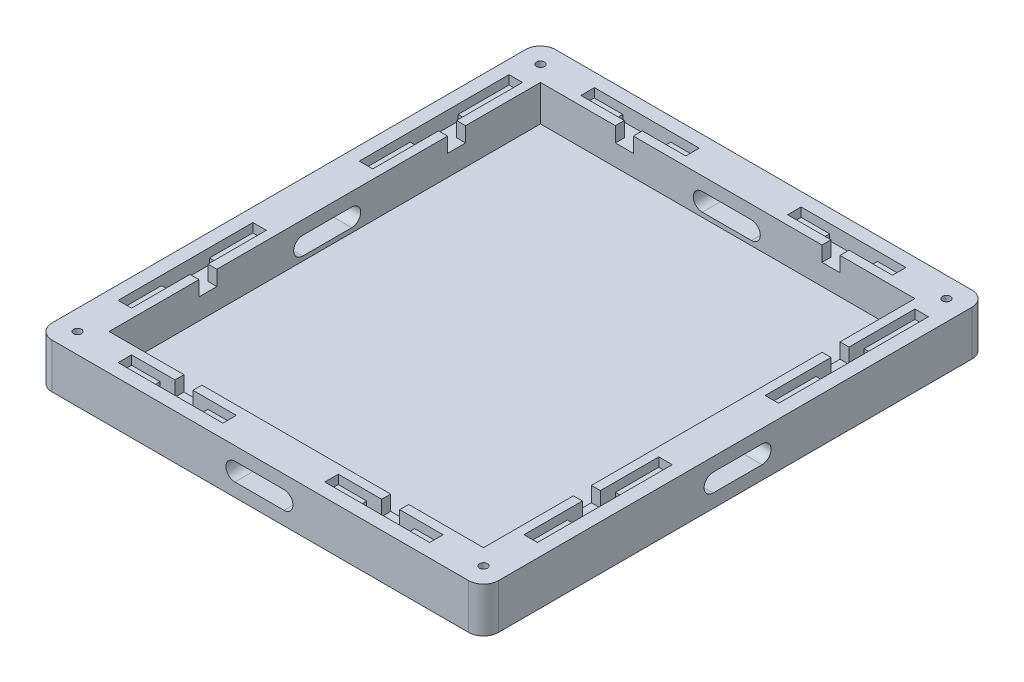
SolidWorks part; units mm, degrees
ref_plane "Front Plane" through (0, 0, 0) normal (0, 0, 1) x (1, 0, 0)
ref_plane "Top Plane" through (0, 0, 0) normal (0, 1, 0) x (1, 0, 0)
ref_plane "Right Plane" through (0, 0, 0) normal (1, 0, 0) x (0, 0, -1)
sketch "Sketch1" plane through (0, 0, 0) normal (0, 1, 0) x (1, 0, 0)
  line L0 (-62.5, 55.915) -> (-62.5, 72)
  line L1 (-47.54, -72) -> (46.365, -72)
  line L2 (-62.5, -57.04) -> (-62.5, 55.915)
  line L3 (-47.54, 72) -> (46.365, 72)
  line L4 (62.5, -57.04) -> (62.5, 55.915)
  line L5 (-62.5, -72) -> (62.5, 72) construction
  line L6 (-62.5, 72) -> (62.5, -72) construction
  line L7 (-62.5, 72) -> (-47.54, 72)
  line L9 (46.365, 72) -> (62.5, 72)
  line L10 (62.5, 72) -> (62.5, 55.915)
  line L12 (62.5, -57.04) -> (62.5, -72)
  line L13 (62.5, -72) -> (46.365, -72)
  line L15 (-47.54, -72) -> (-62.5, -72)
  line L16 (-62.5, -72) -> (-62.5, -57.04)
  line L17 (-74.5, 84) -> (74.5, 84)
  line L18 (74.5, 84) -> (74.5, -84)
  line L19 (74.5, -84) -> (-74.5, -84)
  line L20 (-74.5, -84) -> (-74.5, 84)
  point P0 (0, 0)
  dimension "D3" = 12
  dimension "D5" = 12
  dimension "D4" = 12
  dimension "D6" = 12
  dimension "D1" = 125
  dimension "D2" = 144
extrude "Floor" add sketch "Sketch1" along normal blind 3 contours L16 L2 L0 L7 L3 L9 L10 L4 L12 L13 L1 L15
sketch "Sketch4" plane through (0, 3, 0) normal (0, 1, 0) x (1, 0, 0)
  line L0 (-74.5, 84) -> (74.5, 84)
  line L1 (74.5, 84) -> (74.5, -84)
  line L2 (74.5, -84) -> (-74.5, -84)
  line L3 (-74.5, -84) -> (-74.5, 84)
  line L4 (-62.5, 72) -> (62.5, 72) construction
  line L5 (62.5, 72) -> (62.5, -72) construction
  line L6 (62.5, -72) -> (-62.5, -72) construction
  line L7 (-62.5, -72) -> (-62.5, 72) construction
  line L8 (-62.5, 72) -> (-62.5, -72)
  line L9 (-62.5, -72) -> (62.5, -72)
  line L10 (62.5, -72) -> (62.5, 72)
  line L11 (62.5, 72) -> (-62.5, 72)
  dimension "D1" = 12
  dimension "D2" = 12
  dimension "D3" = 12
  dimension "D4" = 12
extrude "Boss-Extrude1" add sketch "Sketch4" along normal blind 12 and the other way blind 3
fillet "Fillet1" radius 5 1 edges at (-74.5, 7.5, 84)
fillet "Fillet2" radius 5 1 edges at (74.5, 7.5, 84)
fillet "Fillet3" radius 5 1 edges at (74.5, 7.5, -84)
fillet "Fillet4" radius 5 1 edges at (-74.5, 7.5, -84)
sketch "Sketch5" plane through (0, 15, 0) normal (0, 1, 0) x (1, 0, 0)
  line L0 (-62.5, 47) -> (-62.5, 41)
  line L1 (-62.5, 41) -> (-65.5, 41)
  line L2 (-65.5, 41) -> (-65.5, 19)
  line L3 (-65.5, 19) -> (-70, 19)
  line L4 (-70, 19) -> (-70, 69)
  line L5 (-70, 69) -> (-65.5, 69)
  line L6 (-65.5, 69) -> (-65.5, 47)
  line L7 (-65.5, 47) -> (-62.5, 47)
  line L8 (-62.5, 72) -> (-62.5, 47) construction
  line L9 (-62.5, 72) -> (-62.5, -72) construction
  line L10 (-62.5, 72) -> (-62.5, 7) construction
  line L11 (-62.5, -36) -> (-62.5, -42)
  line L12 (-62.5, -42) -> (-65.5, -42)
  line L13 (-65.5, -42) -> (-65.5, -61.5)
  line L14 (-65.5, -61.5) -> (-70, -61.5)
  line L15 (-70, -61.5) -> (-70, -16.5)
  line L16 (-70, -16.5) -> (-65.5, -16.5)
  line L17 (-65.5, -16.5) -> (-65.5, -36)
  line L18 (-65.5, -36) -> (-62.5, -36)
  line L19 (-62.5, 7) -> (-62.5, -7) construction
  line L20 (-62.5, -72) -> (-62.5, -42) construction
  line L21 (-62.5, -72) -> (-62.5, 72) construction
  line L22 (62.5, -36) -> (62.5, -42)
  line L23 (62.5, -42) -> (65.5, -42)
  line L24 (65.5, -42) -> (65.5, -61.5)
  line L25 (65.5, -61.5) -> (70, -61.5)
  line L26 (70, -61.5) -> (70, -16.5)
  line L27 (70, -16.5) -> (65.5, -16.5)
  line L28 (65.5, -16.5) -> (65.5, -36)
  line L29 (65.5, -36) -> (62.5, -36)
  line L30 (62.5, -72) -> (62.5, -42) construction
  line L31 (62.5, -72) -> (62.5, 72) construction
  line L32 (62.5, 47) -> (62.5, 41)
  line L33 (62.5, 41) -> (65.5, 41)
  line L34 (65.5, 41) -> (65.5, 19)
  line L35 (65.5, 19) -> (70, 19)
  line L36 (70, 19) -> (70, 69)
  line L37 (70, 69) -> (65.5, 69)
  line L38 (65.5, 69) -> (65.5, 47)
  line L39 (65.5, 47) -> (62.5, 47)
  line L40 (62.5, 72) -> (62.5, 47) construction
  line L41 (62.5, 72) -> (7, 72) construction
  line L42 (62.5, 72) -> (37.5, 72) construction
  line L43 (62.5, 72) -> (-62.5, 72) construction
  line L44 (-62.5, 72) -> (-6.7, 72) construction
  line L45 (-62.5, 72) -> (-37.5, 72) construction
  line L46 (-37.5, 72) -> (-31.5, 72)
  line L47 (-31.5, 72) -> (-31.5, 75)
  line L48 (-31.5, 75) -> (-17, 75)
  line L49 (-17, 75) -> (-17, 79.5)
  line L50 (-17, 79.5) -> (-52, 79.5)
  line L51 (-52, 79.5) -> (-52, 75)
  line L52 (-52, 75) -> (-37.5, 75)
  line L53 (-37.5, 75) -> (-37.5, 72)
  line L54 (31.5, 72) -> (37.5, 72)
  line L55 (37.5, 72) -> (37.5, 75)
  line L56 (37.5, 75) -> (52, 75)
  line L57 (52, 75) -> (52, 79.5)
  line L58 (52, 79.5) -> (17, 79.5)
  line L59 (17, 79.5) -> (17, 75)
  line L60 (17, 75) -> (31.5, 75)
  line L61 (31.5, 75) -> (31.5, 72)
  line L62 (-37.5, -72) -> (-31.5, -72)
  line L63 (-31.5, -72) -> (-31.5, -75)
  line L64 (-31.5, -75) -> (-17, -75)
  line L65 (-17, -75) -> (-17, -79.5)
  line L66 (-17, -79.5) -> (-52, -79.5)
  line L67 (-52, -79.5) -> (-52, -75)
  line L68 (-52, -75) -> (-37.5, -75)
  line L69 (-37.5, -75) -> (-37.5, -72)
  line L70 (-62.5, -72) -> (-37.5, -72) construction
  line L71 (-62.5, -72) -> (62.5, -72) construction
  line L72 (31.5, -72) -> (37.5, -72)
  line L73 (37.5, -72) -> (37.5, -75)
  line L74 (37.5, -75) -> (52, -75)
  line L75 (52, -75) -> (52, -79.5)
  line L76 (52, -79.5) -> (17, -79.5)
  line L77 (17, -79.5) -> (17, -75)
  line L78 (17, -75) -> (31.5, -75)
  line L79 (31.5, -75) -> (31.5, -72)
  line L80 (62.5, -72) -> (37.5, -72) construction
  line L81 (62.5, -72) -> (-62.5, -72) construction
  dimension "D1" = 6
  dimension "D2" = 3
  dimension "D3" = 4.5
  dimension "D4" = 50
  dimension "D5" = 25
  dimension "D6" = 65
  dimension "D7" = 55.5
  dimension "D8" = 6
  dimension "D9" = 3
  dimension "D10" = 4.5
  dimension "D11" = 45
  dimension "D12" = 14
  dimension "D13" = 30
  dimension "D14" = 6
  dimension "D15" = 3
  dimension "D16" = 4.5
  dimension "D17" = 45
  dimension "D18" = 30
  dimension "D19" = 25
  dimension "D20" = 4.5
  dimension "D21" = 50
  dimension "D22" = 6
  dimension "D23" = 3
  dimension "D24" = 25
  dimension "D25" = 55.8
  dimension "D26" = 25
  dimension "D27" = 6
  dimension "D28" = 3
  dimension "D29" = 4.5
  dimension "D30" = 35
  dimension "D31" = 4.5
  dimension "D32" = 35
  dimension "D33" = 6
  dimension "D34" = 3
  dimension "D35" = 6
  dimension "D36" = 3
  dimension "D37" = 4.5
  dimension "D38" = 35
  dimension "D39" = 25
  dimension "D40" = 3
  dimension "D41" = 4.5
  dimension "D42" = 35
  dimension "D43" = 6
  dimension "D44" = 25
extrude "Cut-Extrude1" cut sketch "Sketch5" against normal blind 3
sketch "Sketch6" plane through (0, 12, 0) normal (0, 1, 0) x (1, 0, 0)
  line L51 (31.5, 72) -> (37.5, 72)
  line L53 (37.5, 72) -> (37.5, 75)
  line L109 (37.5, 75) -> (42.5, 75)
  line L110 (42.5, 75) -> (42.5, 79.5)
  line L111 (42.5, 79.5) -> (26.5, 79.5)
  line L112 (26.5, 79.5) -> (26.5, 75)
  line L113 (26.5, 75) -> (31.5, 75)
  line L114 (31.5, 75) -> (31.5, 72)
  line L115 (62.5, 47) -> (62.5, 41)
  line L116 (62.5, 41) -> (65.5, 41)
  line L117 (65.5, 41) -> (65.5, 36)
  line L118 (65.5, 36) -> (70, 36)
  line L119 (70, 36) -> (70, 52)
  line L120 (70, 52) -> (65.5, 52)
  line L121 (65.5, 52) -> (65.5, 47)
  line L122 (65.5, 47) -> (62.5, 47)
  line L123 (-37.5, 72) -> (-31.5, 72)
  line L124 (-31.5, 72) -> (-31.5, 75)
  line L125 (-31.5, 75) -> (-26.5, 75)
  line L126 (-26.5, 75) -> (-26.5, 79.5)
  line L127 (-26.5, 79.5) -> (-42.5, 79.5)
  line L128 (-42.5, 79.5) -> (-42.5, 75)
  line L129 (-42.5, 75) -> (-37.5, 75)
  line L130 (-37.5, 75) -> (-37.5, 72)
  line L131 (-62.5, 47) -> (-65.5, 47)
  line L132 (-65.5, 47) -> (-65.5, 52)
  line L133 (-65.5, 52) -> (-70, 52)
  line L134 (-70, 52) -> (-70, 36)
  line L135 (-70, 36) -> (-65.5, 36)
  line L136 (-65.5, 36) -> (-65.5, 41)
  line L137 (-65.5, 41) -> (-62.5, 41)
  line L138 (-62.5, 41) -> (-62.5, 47)
  line L139 (-62.5, -36) -> (-65.5, -36)
  line L140 (-65.5, -36) -> (-65.5, -31)
  line L141 (-65.5, -31) -> (-70, -31)
  line L142 (-70, -31) -> (-70, -47)
  line L143 (-70, -47) -> (-65.5, -47)
  line L144 (-65.5, -47) -> (-65.5, -42)
  line L145 (-65.5, -42) -> (-62.5, -42)
  line L146 (-62.5, -42) -> (-62.5, -36)
  line L147 (-37.5, -72) -> (-37.5, -75)
  line L148 (-37.5, -75) -> (-42.5, -75)
  line L149 (-42.5, -75) -> (-42.5, -79.5)
  line L150 (-42.5, -79.5) -> (-26.5, -79.5)
  line L151 (-26.5, -79.5) -> (-26.5, -75)
  line L152 (-26.5, -75) -> (-31.5, -75)
  line L153 (-31.5, -75) -> (-31.5, -72)
  line L154 (-31.5, -72) -> (-37.5, -72)
  line L155 (31.5, -72) -> (31.5, -75)
  line L156 (31.5, -75) -> (26.5, -75)
  line L157 (26.5, -75) -> (26.5, -79.5)
  line L158 (26.5, -79.5) -> (42.5, -79.5)
  line L159 (42.5, -79.5) -> (42.5, -75)
  line L160 (42.5, -75) -> (37.5, -75)
  line L161 (37.5, -75) -> (37.5, -72)
  line L162 (37.5, -72) -> (31.5, -72)
  line L163 (62.5, -36) -> (62.5, -42)
  line L164 (62.5, -42) -> (65.5, -42)
  line L165 (65.5, -42) -> (65.5, -47)
  line L166 (65.5, -47) -> (70, -47)
  line L167 (70, -47) -> (70, -31)
  line L168 (70, -31) -> (65.5, -31)
  line L169 (65.5, -31) -> (65.5, -36)
  line L170 (65.5, -36) -> (62.5, -36)
extrude "Cut-Extrude2" cut sketch "Sketch6" against normal blind 2
sketch "Sketch7" plane through (-74.5, 0, 0) normal (-1, 0, 0) x (0, 0, 1)
  line L0 (-84, 7.5) -> (-12, 7.5) construction
  line L1 (-84, 0) -> (-84, 15) construction
  line L2 (-9, 10.5) -> (7.38, 10.5)
  line L3 (-9, 4.5) -> (7.38, 4.5)
  line L4 (-12, 4.845) -> (-12, 10.155) construction
  arc A0 (-9, 4.5) -> (-9, 10.5) centre (-9, 7.5) cw
  arc A1 (7.38, 10.5) -> (7.38, 4.5) centre (7.38, 7.5) cw
  point P10 (-9, 10.5)
  point P13 (-12, 7.5)
  dimension "D3" = 3
  dimension "D1" = 72
  dimension "D2" = 16.38
extrude "Cut-Extrude3" cut sketch "Sketch7" against normal through all
sketch "Sketch8" plane through (0, 0, 84) normal (0, 0, 1) x (1, 0, 0)
  line L0 (-74.5, 7.5) -> (-11.5, 7.5) construction
  line L1 (-74.5, 0) -> (-74.5, 15) construction
  line L2 (-8.5, 10.5) -> (7.88, 10.5)
  line L3 (-8.5, 4.5) -> (7.88, 4.5)
  line L4 (-11.5, 4.845) -> (-11.5, 10.155) construction
  arc A0 (-8.5, 4.5) -> (-8.5, 10.5) centre (-8.5, 7.5) cw
  arc A1 (7.88, 10.5) -> (7.88, 4.5) centre (7.88, 7.5) cw
  point P10 (-8.5, 10.5)
  point P13 (-11.5, 7.5)
  dimension "D3" = 3
  dimension "D1" = 63
  dimension "D2" = 16.38
extrude "Cut-Extrude4" cut sketch "Sketch8" against normal through all
sketch "Sketch9" plane through (0, 0, 0) normal (0, -1, 0) x (1, 0, 0)
  circle A0 centre (-67.7678, 77.2678) radius 1.325
  circle A1 centre (67.7678, 77.2678) radius 1.325
  circle A2 centre (67.7678, -77.2678) radius 1.325
  circle A3 centre (-67.7678, -77.2678) radius 1.325
  dimension "D1" = 2.65
  dimension "D2" = 2.65
  dimension "D3" = 2.65
  dimension "D4" = 2.65
extrude "Cut-Extrude5" cut sketch "Sketch9" against normal blind 17
sketch "Sketch10" plane through (0, 0, 0) normal (0, -1, 0) x (1, 0, 0)
  circle A0 centre (-67.7678, 77.2678) radius 3
  circle A1 centre (67.7678, 77.2678) radius 3
  circle A2 centre (67.7678, -77.2678) radius 3
  circle A3 centre (-67.7678, -77.2678) radius 3
  dimension "D1" = 6
  dimension "D2" = 6
  dimension "D3" = 6
  dimension "D4" = 6
extrude "Cut-Extrude6" cut sketch "Sketch10" against normal blind 5
sketch "Sketch11" plane through (0, 0, 0) normal (0, -1, 0) x (1, 0, 0)
  line L0 (-62.5, 72) -> (-62.5, -72) construction
  line L1 (62.5, 72) -> (-62.5, 72) construction
  line L2 (62.5, -72) -> (62.5, 72) construction
  line L3 (-62.5, -72) -> (62.5, -72) construction
  circle A0 centre (-42.5, 52) radius 6.25
  circle A1 centre (42.5, 52) radius 6.25
  circle A2 centre (-42.5, -52) radius 6.25
  circle A3 centre (42.5, -52) radius 6.25
  point P12 (0, 0)
  point P15 (0, 0)
  dimension "D1" = 12.5
  dimension "D2" = 12.5
  dimension "D3" = 12.5
  dimension "D4" = 12.5
  dimension "D5" = 20
  dimension "D6" = 20
  dimension "D7" = 20
  dimension "D8" = 20
  dimension "D9" = 20
  dimension "D10" = 20
  dimension "D11" = 20
  dimension "D12" = 20
extrude "Cut-Extrude7" cut sketch "Sketch11" against normal blind 1
